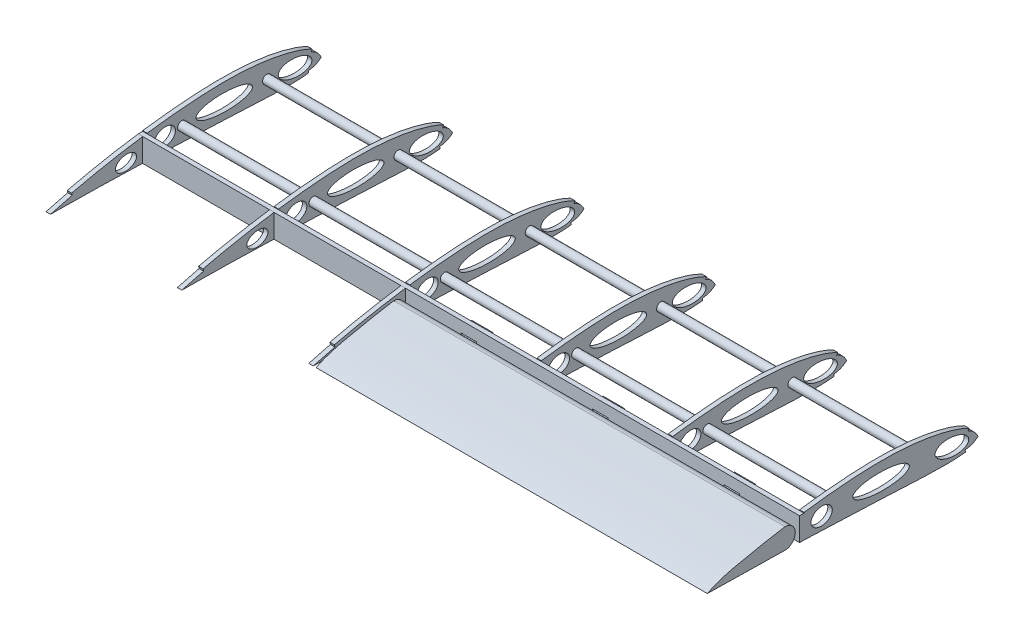
SolidWorks part; units mm, degrees
ref_plane "Front Plane" through (0, 0, 0) normal (0, 0, 1) x (1, 0, 0)
ref_plane "Top Plane" through (0, 0, 0) normal (0, 1, 0) x (1, 0, 0)
ref_plane "Right Plane" through (0, 0, 0) normal (1, 0, 0) x (0, 0, -1)
curve "Curve1"
  spline degree 3 poles (0, 0.2561, 197) (0, 1.149, 193.7201) (0, 2.9304, 187.176) (0, 6.1695, 174.0663) (0, 9.7483, 157.6722) (0, 13.2762, 137.9533) (0, 16.1679, 118.2496) (0, 18.2306, 98.5349) (0, 19.5171, 78.822) (0, 19.5301, 62.3654) (0, 18.621, 49.2257) (0, 17.4237, 39.3576) (0, 15.6579, 29.4682) (0, 13.5343, 21.2733) (0, 11.3895, 14.7062) (0, 9.3648, 9.7544) (0, 7.1751, 5.5294) (0, 4.5558, 1.862) (0, 0.3432, -1.3305) (0, -2.8786, 2.1154) (0, -4.1432, 5.6315) (0, -4.9968, 9.819) (0, -5.4308, 14.7645) (0, -5.7379, 21.3389) (0, -5.7149, 29.5521) (0, -5.4392, 39.4043) (0, -4.9143, 49.2495) (0, -4.3, 62.3829) (0, -3.5118, 78.7969) (0, -2.7716, 98.5006) (0, -1.9498, 118.198) (0, -1.2497, 137.8972) (0, -0.7348, 157.5981) (0, -0.4734, 174.0162) (0, -0.3012, 187.1497) (0, -0.2711, 193.7166) (0, -0.2561, 197) knots 0 0 0 0 0.025305 0.050488 0.10052 0.150191 0.199587 0.24874 0.297716 0.346601 0.371103 0.395726 0.42057 0.445825 0.458702 0.47192 0.485786 0.493461 0.506863 0.516148 0.522766 0.535269 0.547551 0.559786 0.584229 0.608681 0.633151 0.657622 0.706558 0.755482 0.804406 0.85332 0.902221 0.951113 0.975557 1 1 1 1
sketch "Sketch2" plane through (0, 0, 0) normal (1, 0, 0) x (0, 0, -1)
  line L0 (-197, 0.2561) -> (-197, -0.2561)
  line L1 (-197, 0) -> (0, 0) construction
  line L2 (-40, 17.4248) -> (-40, -5.373) construction
  line L3 (-100, 17.9747) -> (-100, -2.6983) construction
  line L4 (0, 0) -> (-40, 6.0259) construction
  line L5 (-40, 6.0259) -> (-100, 7.6382) construction
  line L6 (-100, 7.6382) -> (-197, 0) construction
  line L8 (-124.4398, 15.2116) -> (-124.4398, -1.7354)
  line L11 (-124.4398, 15.2116) -> (-127.6098, 15.2116)
  line L12 (-124.4398, 15.2116) -> (-124.4398, 8.8616)
  line L13 (-124.4398, 8.8616) -> (-127.6098, 8.8616)
  line L14 (-127.6098, 15.2116) -> (-127.6098, 8.8616)
  circle A0 centre (-100, 7.6382) radius 3
  circle A1 centre (-40, 6.0259) radius 3
  ellipse E0 centre (-70, 6.8321) end of major axis (-50.0072, 6.2948) minor radius 6.0022
  ellipse E1 centre (-20, 3.013) end of major axis (-31.8661, 4.8006) minor radius 6
  ellipse E2 centre (-111.963, 6.6962) end of major axis (-104.4861, 7.285) minor radius 6
  ellipse E3 centre (-139.3781, 4.5374) end of major axis (-131.9012, 5.1262) minor radius 5
  spline S0 degree 3 poles (-1051.5232, 1795.2139) (-419.8034, -115.8999) (-307.734, -26.8568) (-174.0663, 6.1695) (-157.6722, 9.7483) (-137.9533, 13.2762) (-118.2496, 16.1679) (-98.5349, 18.2306) (-78.822, 19.5171) (-62.3654, 19.5301) (-49.2257, 18.621) (-39.3576, 17.4237) (-29.4682, 15.6579) (-21.2733, 13.5343) (-14.7062, 11.3895) (-9.7544, 9.3648) (-5.5294, 7.1751) (-1.862, 4.5558) (1.3305, 0.3432) (-2.1154, -2.8786) (-5.6315, -4.1432) (-9.819, -4.9968) (-14.7645, -5.4308) (-21.3389, -5.7379) (-29.5521, -5.7149) (-39.4043, -5.4392) (-49.2495, -4.9143) (-62.3829, -4.3) (-78.7969, -3.5118) (-98.5006, -2.7716) (-118.198, -1.9498) (-137.8972, -1.2497) (-157.5981, -0.7348) (-174.0162, -0.4734) (-356.257, 1.9157) (-532.2805, -35.874) (-687.6692, 1915.6634) knots -0.924398 -0.924398 -0.924398 -0.924398 0.025305 0.050488 0.10052 0.150191 0.199587 0.24874 0.297716 0.346601 0.371103 0.395726 0.42057 0.445825 0.458702 0.47192 0.485786 0.493461 0.506863 0.516148 0.522766 0.535269 0.547551 0.559786 0.584229 0.608681 0.633151 0.657622 0.706558 0.755482 0.804406 0.85332 0.902221 0.951113 0.975557 2.258998 2.258998 2.258998 2.258998 only from (-197, 0.2561) to (-197, -0.2561) construction
  spline S1 degree 3 poles (-197, 0.2561) (-193.7201, 1.149) (-187.176, 2.9304) (-174.0663, 6.1695) (-157.6722, 9.7483) (-137.9533, 13.2762) (-118.2496, 16.1679) (-98.5349, 18.2306) (-78.822, 19.5171) (-62.3654, 19.5301) (-49.2257, 18.621) (-39.3576, 17.4237) (-29.4682, 15.6579) (-21.2733, 13.5343) (-14.7062, 11.3895) (-9.7544, 9.3648) (-5.5294, 7.1751) (-1.862, 4.5558) (1.3305, 0.3432) (-2.1154, -2.8786) (-5.6315, -4.1432) (-9.819, -4.9968) (-14.7645, -5.4308) (-21.3389, -5.7379) (-29.5521, -5.7149) (-39.4043, -5.4392) (-49.2495, -4.9143) (-62.3829, -4.3) (-78.7969, -3.5118) (-98.5006, -2.7716) (-118.198, -1.9498) (-137.8972, -1.2497) (-157.5981, -0.7348) (-174.0162, -0.4734) (-187.1497, -0.3012) (-193.7166, -0.2711) (-197, -0.2561) knots 0 0 0 0 0.025305 0.050488 0.10052 0.150191 0.199587 0.24874 0.297716 0.346601 0.371103 0.395726 0.42057 0.445825 0.458702 0.47192 0.485786 0.493461 0.506863 0.516148 0.522766 0.535269 0.547551 0.559786 0.584229 0.608681 0.633151 0.657622 0.706558 0.755482 0.804406 0.85332 0.902221 0.951113 0.975557 1 1 1 1
  point P36 (-98.5, 0)
  point P42 (-69.8388, 12.8321)
  point P43 (0, 0)
  point P45 (-69.8388, 19.4612)
  dimension "D3" = 6
  dimension "D4" = 6
  dimension "D12" = 5
  dimension "D13" = 3.17
  dimension "D17" = 15
  dimension "D1" = 40
  dimension "D2" = 60
  dimension "D5" = 40
  dimension "D6" = 12
  dimension "D7" = 12
  dimension "D8" = 15
  dimension "D9" = 12
  dimension "D10" = 24
  dimension "D11" = 12
  dimension "D15" = 20
  dimension "D16" = 10
  dimension "D14" = 6.35
extrude "Spars" add sketch "Sketch2" along normal blind 467 contours A1 | A0
extrude "Base Wing" add sketch "Sketch2<9>" along normal blind 3.175 contours A0 | E0 | A1 | E2 | E1 | S1 L0 | E3
sketch "Sketch2<9>" plane through (0, 0, 0) normal (1, 0, 0) x (0, 0, -1) same geometry as "Sketch2"
sketch "Sketch3" plane through (3.175, 0, 0) normal (1, 0, 0) x (0, 0, -1)
  line L0 (-197.1241, 0.224) -> (-177.7605, 5.2292)
  line L1 (-177.7605, 5.2292) -> (-197.1241, 0.224) construction
  line L2 (-177.7605, 5.2292) -> (-177.3632, 3.6922) construction
  line L3 (-197.1241, 0.224) -> (-196.7268, -1.313) construction
  line L4 (-177.3632, 3.6922) -> (-196.7268, -1.313) construction
  line L5 (0, 0) -> (-1.5698, 0.2365) construction
  line L6 (0, 0) -> (-40, 6.0259) construction
  line L7 (-7.8655, 8.3531) -> (-8.591, 6.9411)
  line L8 (-4.3591, 4.3441) -> (-3.3767, 5.5912) construction
  line L9 (-8.591, 6.9411) -> (-4.3591, 4.3441) construction
  line L10 (-4.3591, 4.3441) -> (-1.5698, 0.2365) construction
  line L11 (-5.3287, -3.9604) -> (-5.7651, -2.434) construction
  line L12 (-10.4332, -4.9861) -> (-10.6411, -3.4123)
  line L13 (-3.3767, 5.5912) -> (-2.3943, 6.8382)
  line L14 (-1.5698, 0.2365) -> (-5.7651, -2.434) construction
  line L15 (-10.6411, -3.4123) -> (-5.7651, -2.434) construction
  line L16 (0, 0) -> (1.5698, -0.2365)
  line L17 (-5.3287, -3.9604) -> (-4.8922, -5.4867)
  line L18 (-197.1241, 0.224) -> (-177.7605, 5.2292) construction
  line L23 (-197.1241, 0.224) -> (-197.5214, 1.761) construction
  line L24 (-177.7605, 5.2292) -> (-178.1578, 6.7662) construction
  line L25 (-197.5214, 1.761) -> (-178.1578, 6.7662) construction
  line L26 (-197.5214, 1.761) -> (-196.7268, -1.313)
  line L27 (-197.5214, 1.761) -> (-178.1578, 6.7662)
  line L28 (-196.7268, -1.313) -> (-177.3632, 3.6922)
  line L29 (-178.1578, 6.7662) -> (-177.3632, 3.6922)
  spline S0 degree 3 poles (-197, 0.2561) (-193.7201, 1.149) (-187.176, 2.9304) (-174.0663, 6.1695) (-157.6722, 9.7483) (-137.9533, 13.2762) (-118.2496, 16.1679) (-98.5349, 18.2306) (-78.822, 19.5171) (-62.3654, 19.5301) (-49.2257, 18.621) (-39.3576, 17.4237) (-29.4682, 15.6579) (-21.2733, 13.5343) (-14.7062, 11.3895) (-9.7544, 9.3648) (-5.5294, 7.1751) (-1.862, 4.5558) (1.3305, 0.3432) (-2.1154, -2.8786) (-5.6315, -4.1432) (-9.819, -4.9968) (-14.7645, -5.4308) (-21.3389, -5.7379) (-29.5521, -5.7149) (-39.4043, -5.4392) (-49.2495, -4.9143) (-62.3829, -4.3) (-78.7969, -3.5118) (-98.5006, -2.7716) (-118.198, -1.9498) (-137.8972, -1.2497) (-157.5981, -0.7348) (-174.0162, -0.4734) (-187.1497, -0.3012) (-193.7166, -0.2711) (-197, -0.2561) knots 0 0 0 0 0.025305 0.050488 0.10052 0.150191 0.199587 0.24874 0.297716 0.346601 0.371103 0.395726 0.42057 0.445825 0.458702 0.47192 0.485786 0.493461 0.506863 0.516148 0.522766 0.535269 0.547551 0.559786 0.584229 0.608681 0.633151 0.657622 0.706558 0.755482 0.804406 0.85332 0.902221 0.951113 0.975557 1 1 1 1 construction
  spline S1 degree 2 poles (-8.591, 6.9411) (-3.6378, 5.0995) (-1.5698, 0.2365) knots 0 0 0 1 1 1
  spline S2 degree 2 poles (-10.6411, -3.4123) (-5.4248, -3.2802) (-1.5698, 0.2365) knots 0 0 0 1 1 1
  spline S3 degree 3 poles (-7.8655, 8.3531) (-3.7436, 9.3316) (8.4481, -1.5787) (-6.8965, -7.2435) (-10.4332, -4.9861) knots 0 0 0 0 0.49814 1 1 1 1
  point P5 (-7.8655, 8.3531)
  point P25 (-10.4332, -4.9861)
  point P26 (-5.3287, -3.9604)
  point P27 (0, 0)
  dimension "D6" = 10
  dimension "D4" = 10
  dimension "D1" = 1.5875
  dimension "D2" = 20
  dimension "D3" = 1.5875
  dimension "D5" = 1.5875
pattern_linear "LPattern7" count 3 spacing 92.765 along (1, 0, 0) of "Base Wing"
extrude "Trailing Edge" cut sketch "Sketch3" against normal blind 3.175 contours L27 L29 L28 L26
extrude "Leading Edge" cut sketch "Sketch3<8>" against normal blind 3.175 contours S3 L12 S2 S1 L7
sketch "Sketch3<8>" plane through (3.175, 0, 0) normal (1, 0, 0) x (0, 0, -1) same geometry as "Sketch3"
pattern_linear "LPattern8" count 3 spacing 92.765 along (1, 0, 0) of "Trailing Edge", "Leading Edge"
extrude "Face" cut sketch "Sketch2<10>" along normal blind 3.175 contours L11 L14 L13 L12
sketch "Sketch2<10>" plane through (0, 0, 0) normal (1, 0, 0) x (0, 0, -1) same geometry as "Sketch2"
pattern_linear "LPattern9" count 3 spacing 92.765 along (1, 0, 0) of "Face"
ref_plane "SparPlane" through (0, 0, 127.6098) normal (0, 0, -1) x (-1, 0, 0)
sketch "Sketch12" plane through (0, 0, 127.6098) normal (0, 0, -1) x (-1, 0, 0)
  line L0 (0, 14.7629) -> (0, 8.8616)
  line L1 (0, 8.8616) -> (-3.175, 8.8616)
  line L2 (-3.175, 8.8616) -> (-3.175, -1.7384)
  line L3 (0, 14.7629) -> (-467, 14.7629)
  line L4 (-3.175, -1.7384) -> (-92.765, -1.7384)
  line L5 (-92.765, -1.7384) -> (-92.765, 8.8616)
  line L6 (-92.765, 8.8616) -> (-95.94, 8.8616)
  line L7 (-95.94, 8.8616) -> (-95.94, -1.7384)
  line L8 (-95.94, -1.7384) -> (-185.53, -1.7384)
  line L9 (-185.53, -1.7384) -> (-185.53, 8.8616)
  line L10 (-185.53, 8.8616) -> (-188.705, 8.8616)
  line L11 (-188.705, 8.8616) -> (-188.705, -1.7384)
  line L14 (-188.705, -1.7384) -> (-278.295, -1.7384)
  line L15 (-278.295, -1.7384) -> (-278.295, 8.8616)
  line L16 (-278.295, 8.8616) -> (-281.47, 8.8616)
  line L17 (-281.47, 8.8616) -> (-281.47, -1.7384)
  line L18 (-281.47, -1.7384) -> (-371.06, -1.7384)
  line L19 (-371.06, -1.7384) -> (-371.06, 8.8616)
  line L20 (-371.06, 8.8616) -> (-374.235, 8.8616)
  line L21 (-374.235, 8.8616) -> (-374.235, -1.7384)
  line L23 (-374.235, -1.7384) -> (-463.825, -1.7384)
  line L24 (-463.825, -1.7384) -> (-463.825, 8.8616)
  line L25 (-463.825, 8.8616) -> (-467, 8.8616)
  line L26 (-467, 8.8616) -> (-467, 14.7629)
  line L27 (-463.825, 14.7629) -> (-463.825, 8.8616) construction
  line L28 (-188.705, 14.7629) -> (-188.705, -1.7384) construction
  line L29 (-278.295, 14.7629) -> (-278.295, -1.7384) construction
  line L30 (-281.47, 14.7629) -> (-281.47, -1.7384) construction
  line L31 (-371.06, 14.7629) -> (-371.06, -1.7384) construction
  line L32 (-374.235, 14.7629) -> (-374.235, -1.7384) construction
  line L33 (-188.705, 6.5122) -> (-278.295, 6.5122)
  line L34 (-281.47, 6.5122) -> (-371.06, 6.5122)
  line L35 (-374.235, 6.5122) -> (-463.825, 6.5122)
  line L36 (-228, 6.0122) -> (-228, 7.0122)
  line L37 (-228, 6.0122) -> (-239, 6.0122)
  line L38 (-228, 7.0122) -> (-239, 7.0122)
  line L39 (-239, 6.0122) -> (-239, 7.0122)
  line L40 (-228, 6.0122) -> (-239, 7.0122) construction
  line L41 (-228, 7.0122) -> (-239, 6.0122) construction
  line L46 (-318.765, 4.0122) -> (-318.765, 9.0122)
  line L47 (-318.765, 9.0122) -> (-333.765, 9.0122)
  line L52 (-333.765, 4.0122) -> (-333.765, 9.0122)
  line L53 (-318.765, 4.0122) -> (-333.765, 4.0122)
  line L54 (-226, 4.0122) -> (-226, 9.0122)
  line L55 (-226, 9.0122) -> (-241, 9.0122)
  line L56 (-241, 4.0122) -> (-241, 9.0122)
  line L57 (-226, 4.0122) -> (-241, 4.0122)
  line L58 (-320.765, 6.0122) -> (-320.765, 7.0122)
  line L59 (-320.765, 6.0122) -> (-331.765, 6.0122)
  line L60 (-331.765, 6.0122) -> (-331.765, 7.0122)
  line L61 (-320.765, 7.0122) -> (-331.765, 7.0122)
  line L62 (-320.765, 6.0122) -> (-331.765, 7.0122) construction
  line L63 (-320.765, 7.0122) -> (-331.765, 6.0122) construction
  line L64 (-411.53, 4.0122) -> (-411.53, 9.0122)
  line L65 (-411.53, 9.0122) -> (-426.53, 9.0122)
  line L66 (-426.53, 4.0122) -> (-426.53, 9.0122)
  line L67 (-411.53, 4.0122) -> (-426.53, 4.0122)
  line L68 (-413.53, 6.0122) -> (-413.53, 7.0122)
  line L69 (-413.53, 6.0122) -> (-424.53, 6.0122)
  line L70 (-424.53, 6.0122) -> (-424.53, 7.0122)
  line L71 (-413.53, 7.0122) -> (-424.53, 7.0122)
  line L72 (-413.53, 6.0122) -> (-424.53, 7.0122) construction
  line L73 (-413.53, 7.0122) -> (-424.53, 6.0122) construction
  point P44 (-233.5, 6.5122)
  point P46 (-419.03, 6.5122)
  point P51 (-326.265, 6.5122)
  point P55 (-326.265, 6.5122)
  point P65 (-419.03, 6.5122)
  dimension "D1" = 467
  dimension "D2" = 10.6
  dimension "D3" = 92.765
  dimension "D4" = 11
  dimension "D5" = 1
  dimension "D6" = 2
  dimension "D7" = 3
extrude "Balsa Spar" add sketch "Sketch12" along normal blind 3.175 contours L3 L26 L25 L24 L23 L21 L20 L19 L18 L17 L16 L15 L14 L11 L10 L9 L8 L7 L6 L5 L4 L2 L1 L0
ref_plane "Secondary Plane" through (278.295, 0, 0) normal (1, 0, 0) x (0, 0, -1)
sketch "Sketch13" plane through (278.295, 0, 0) normal (1, 0, 0) x (0, 0, -1)
  line L0 (-127.6098, 8.8616) -> (-124.4398, 8.8616)
  line L1 (-127.6098, 8.8616) -> (-127.6098, -1.7384)
  line L2 (-127.6098, -1.7384) -> (-124.4348, -1.7356)
  line L3 (-124.4398, 8.8616) -> (-124.4398, 14.7629)
  line L4 (-124.4398, 15.2116) -> (-124.4398, 14.7629)
  line L6 (-124.4398, 14.7629) -> (-124.4348, 14.7629)
  line L7 (-124.4348, 14.7629) -> (-124.4348, -1.7356)
  line L11 (-124.4398, 14.7629) -> (-124.4348, 14.7629)
  line L15 (-124.4398, 14.7629) -> (-124.4398, 8.8616)
  line L16 (-124.4398, 15.2116) -> (-124.4398, 14.7629)
  line L17 (-124.4398, 15.2116) -> (-124.4398, 14.7629)
  line L20 (-10.4332, -4.9861) -> (-10.6411, -3.4123)
  line L21 (-10.4332, -4.9861) -> (-10.6411, -3.4123)
  line L22 (-8.591, 6.9411) -> (-7.8655, 8.3531)
  line L23 (-8.591, 6.9411) -> (-7.8655, 8.3531)
  circle A0 centre (-40, 6.0259) radius 3 construction
  circle A1 centre (-40, 6.0259) radius 3
  circle A2 centre (-100, 7.6382) radius 3 construction
  circle A3 centre (-100, 7.6382) radius 3
  ellipse E0 centre (-111.963, 6.6962) end of major axis (-104.4861, 7.285) minor radius 6 construction
  ellipse E1 centre (-70, 6.8321) end of major axis (-50.0072, 6.2948) minor radius 6.0022 construction
  ellipse E2 centre (-20, 3.013) end of major axis (-8.1339, 1.2254) minor radius 6 construction
  ellipse E3 centre (-111.963, 6.6962) end of major axis (-104.4861, 7.285) minor radius 6
  ellipse E4 centre (-70, 6.8321) end of major axis (-50.0072, 6.2948) minor radius 6.0022
  ellipse E5 centre (-20, 3.013) end of major axis (-8.1339, 1.2254) minor radius 6
  parabola Q2 (-10.6411, -3.4123) -> (-1.5698, 0.2365) focus (-8.21, 3.6444) apex (-5.7651, -2.434)
  parabola Q3 (-10.6411, -3.4123) -> (-1.5698, 0.2365) focus (-8.21, 3.6444) apex (-5.7651, -2.434)
  parabola Q4 (-1.5698, 0.2365) -> (-8.591, 6.9411) focus (-8.2542, 0.2651) apex (-4.3591, 4.3441)
  parabola Q5 (-1.5698, 0.2365) -> (-8.591, 6.9411) focus (-8.2542, 0.2651) apex (-4.3591, 4.3441)
  spline S2 degree 3 poles (-1367.7155, -2590.3642) (-923.6568, -46.7157) (-512.7824, 14.5145) (-98.5006, -2.7716) (-78.7969, -3.5118) (-62.3829, -4.3) (-49.2495, -4.9143) (-39.4043, -5.4392) (-29.5521, -5.7149) (-21.3389, -5.7379) (43.0686, -2.729) (98.3082, 46.1829) (278.6729, 2978.1004) knots -2.436694 -2.436694 -2.436694 -2.436694 0.552208 0.601132 0.650055 0.698992 0.723462 0.747933 0.772385 0.796827 0.809062 1.252024 1.252024 1.252024 1.252024 only from (-124.4348, -1.7356) to (-10.4332, -4.9861)
  spline S3 degree 3 poles (-2916.9485, -710.3536) (73.3325, -105.9441) (37.3308, -9.8882) (-14.7062, 11.3895) (-21.2733, 13.5343) (-29.4682, 15.6579) (-39.3576, 17.4237) (-49.2257, 18.621) (-62.3654, 19.5301) (-78.822, 19.5171) (-98.5349, 18.2306) (-428.5049, -16.293) (-710.2974, -378.6878) (-1008.0238, 2779.7932) knots -0.204448 -0.204448 -0.204448 -0.204448 0.1894 0.202617 0.215494 0.240749 0.265593 0.290217 0.314719 0.363604 0.412579 0.461733 2.832769 2.832769 2.832769 2.832769 only from (-7.8655, 8.3531) to (-124.4398, 15.2116)
  spline S4 degree 3 poles (-124.4348, -1.7356) (-122.3565, -1.8115) (-113.7109, -2.137) (-98.5006, -2.7716) (-78.7969, -3.5118) (-62.3829, -4.3) (-49.2495, -4.9143) (-39.4043, -5.4392) (-29.5521, -5.7149) (-21.3389, -5.7379) (-14.96, -5.4399) (-11.8784, -5.177) (-10.4332, -4.9861) knots 0.536725 0.536725 0.536725 0.536725 0.552208 0.601132 0.650055 0.698992 0.723462 0.747933 0.772385 0.796827 0.809062 0.819888 0.819888 0.819888 0.819888
  spline S5 degree 3 poles (-7.8655, 8.3531) (-8.5192, 8.689) (-10.7997, 9.7922) (-14.7062, 11.3895) (-21.2733, 13.5343) (-29.4682, 15.6579) (-39.3576, 17.4237) (-49.2257, 18.621) (-62.3654, 19.5301) (-78.822, 19.5171) (-98.5349, 18.2306) (-113.7356, 16.6402) (-122.3616, 15.4993) (-124.4398, 15.2116) knots 0.183969 0.183969 0.183969 0.183969 0.1894 0.202617 0.215494 0.240749 0.265593 0.290217 0.314719 0.363604 0.412579 0.461733 0.477351 0.477351 0.477351 0.477351
  dimension "D1" = 0
extrude "Secondary Base Wing" add sketch "Sketch13" along normal blind 3.175 contours L3 L0 L1 L2 S4 L21 Q3 Q5 L23 S5 L17 | E4 | E3 | E5 | A1 | A3
pattern_linear "LPattern11" count 3 spacing 92.765 along (1, 0, 0) of "Secondary Base Wing"
ref_plane "Insert Plane" through (0, 0, 124.4348) normal (0, 0, -1) x (-1, 0, 0)
sketch "Sketch15" plane through (0, 0, 124.4348) normal (0, 0, -1) x (-1, 0, 0)
  line L0 (-413.53, 6.0122) -> (-413.53, 7.0122) construction
  line L1 (-413.53, 6.0122) -> (-424.53, 6.0122) construction
  line L2 (-424.53, 6.0122) -> (-424.53, 7.0122) construction
  line L3 (-413.53, 7.0122) -> (-424.53, 7.0122) construction
  line L4 (-426.53, 4.0122) -> (-426.53, 9.0122) construction
  line L5 (-411.53, 4.0122) -> (-426.53, 4.0122) construction
  line L6 (-411.53, 4.0122) -> (-411.53, 9.0122) construction
  line L7 (-411.53, 9.0122) -> (-426.53, 9.0122) construction
  line L8 (-228, 6.0122) -> (-228, 7.0122) construction
  line L9 (-228, 6.0122) -> (-239, 6.0122) construction
  line L10 (-239, 6.0122) -> (-239, 7.0122) construction
  line L11 (-228, 7.0122) -> (-239, 7.0122) construction
  line L12 (-241, 4.0122) -> (-241, 9.0122) construction
  line L13 (-226, 4.0122) -> (-241, 4.0122) construction
  line L14 (-226, 4.0122) -> (-226, 9.0122) construction
  line L15 (-226, 9.0122) -> (-241, 9.0122) construction
  line L16 (-318.765, 4.0122) -> (-318.765, 9.0122) construction
  line L17 (-318.765, 4.0122) -> (-333.765, 4.0122) construction
  line L18 (-333.765, 4.0122) -> (-333.765, 9.0122) construction
  line L19 (-318.765, 9.0122) -> (-333.765, 9.0122) construction
  line L20 (-331.765, 6.0122) -> (-331.765, 7.0122) construction
  line L21 (-320.765, 6.0122) -> (-331.765, 6.0122) construction
  line L22 (-320.765, 7.0122) -> (-331.765, 7.0122) construction
  line L23 (-320.765, 6.0122) -> (-320.765, 7.0122) construction
  line L24 (-413.53, 6.0122) -> (-413.53, 7.0122)
  line L25 (-413.53, 6.0122) -> (-424.53, 6.0122)
  line L26 (-424.53, 6.0122) -> (-424.53, 7.0122)
  line L27 (-413.53, 7.0122) -> (-424.53, 7.0122)
  line L28 (-426.53, 4.0122) -> (-426.53, 9.0122)
  line L29 (-411.53, 4.0122) -> (-426.53, 4.0122)
  line L30 (-411.53, 4.0122) -> (-411.53, 9.0122)
  line L31 (-411.53, 9.0122) -> (-426.53, 9.0122)
  line L32 (-228, 6.0122) -> (-228, 7.0122)
  line L33 (-228, 6.0122) -> (-239, 6.0122)
  line L34 (-239, 6.0122) -> (-239, 7.0122)
  line L35 (-228, 7.0122) -> (-239, 7.0122)
  line L36 (-241, 4.0122) -> (-241, 9.0122)
  line L37 (-226, 4.0122) -> (-241, 4.0122)
  line L38 (-226, 4.0122) -> (-226, 9.0122)
  line L39 (-226, 9.0122) -> (-241, 9.0122)
  line L40 (-318.765, 4.0122) -> (-318.765, 9.0122)
  line L41 (-318.765, 4.0122) -> (-333.765, 4.0122)
  line L42 (-333.765, 4.0122) -> (-333.765, 9.0122)
  line L43 (-318.765, 9.0122) -> (-333.765, 9.0122)
  line L44 (-331.765, 6.0122) -> (-331.765, 7.0122)
  line L45 (-320.765, 6.0122) -> (-331.765, 6.0122)
  line L46 (-320.765, 7.0122) -> (-331.765, 7.0122)
  line L47 (-320.765, 6.0122) -> (-320.765, 7.0122)
extrude "Inserts" add sketch "Sketch15" along normal blind 3.175
pattern_linear "LPattern12" count 2 spacing 3.175 along (0, 0, -1) of "Inserts"
ref_plane "Aileron Plane" through (190.705, 0, 0) normal (1, 0, 0) x (0, 0, -1)
sketch "Sketch17" plane through (190.705, 0, 0) normal (1, 0, 0) x (0, 0, -1)
  line L0 (-137.845, -1.2822) -> (-137.845, 13.1882) construction
  line L1 (-137.845, 5.953) -> (-192.7184, -0.2769) construction
  line L2 (-165.2817, 2.8381) -> (-165.8594, 7.9262) construction
  line L3 (-127.6098, -1.6216) -> (-127.6098, 14.7629)
  line L4 (-177.7605, 5.2292) -> (-177.3632, 3.6922)
  line L5 (-177.3632, 3.6922) -> (-192.7184, -0.2769)
  line L6 (-127.6098, -1.6216) -> (-127.6098, 14.7629)
  line L7 (-177.7605, 5.2292) -> (-177.3632, 3.6922)
  line L8 (-177.3632, 3.6922) -> (-192.7184, -0.2769)
  line L9 (-165.2817, 2.8381) -> (-137.845, 5.953) construction
  line L10 (-165.2817, 2.8381) -> (-137.845, 5.953) construction
  line L11 (-137.845, 5.953) -> (-151.5634, 4.3956) construction
  line L12 (-151.5634, 4.3956) -> (-152.2748, 10.6623) construction
  line L13 (-192.7184, -0.2769) -> (-137.845, -1.2822)
  arc A0 (-137.845, 13.1882) -> (-137.845, -1.2822) centre (-137.845, 5.953) cw
  spline S0 degree 1 poles (-137.845, 13.1882) (-152.2748, 10.6623) knots 0 0 1 1
  spline S1 degree 3 poles (-137.845, 13.1882) (-147.2462, 11.7369) (-165.7323, 8) (-184.2505, 4.0667) (-192.7184, -0.2769) knots 0 0 0 0 0.503218 1 1 1 1
  spline S2 degree 3 poles (-755.0077, 2911.5208) (-583.0658, -47.6094) (-381.5956, 2.2478) (-174.0162, -0.4734) (-157.5981, -0.7348) (284.8785, -12.2997) (716.4734, -159.5093) (1182.3538, 2510.7435) knots -0.630495 -0.630495 -0.630495 -0.630495 0.84159 0.866034 0.914926 0.963827 4.161051 4.161051 4.161051 4.161051 only from (-192.7184, -0.2769) to (-127.6098, -1.6216)
  spline S3 degree 3 poles (793.2444, -2775.7791) (428.7441, -71.8713) (123.9697, 60.136) (-157.6722, 9.7483) (-388.6317, -40.6699) (-579.8547, -228.2766) (82.11, -2940.561) knots -1.9547 -1.9547 -1.9547 -1.9547 0.075147 0.124817 0.17485 1.834535 1.834535 1.834535 1.834535 only from (-127.6098, 14.7629) to (-177.7605, 5.2292)
  spline S4 degree 3 poles (-192.7184, -0.2769) (-190.8622, -0.2868) (-185.7226, -0.3199) (-174.0162, -0.4734) (-157.5981, -0.7348) (-141.035, -1.1677) (-131.0396, -1.5005) (-127.6098, -1.6216) knots 0.827772 0.827772 0.827772 0.827772 0.84159 0.866034 0.914926 0.963827 0.989375 0.989375 0.989375 0.989375
  spline S5 degree 3 poles (-127.6098, 14.7629) (-131.0445, 14.2663) (-141.0695, 12.7187) (-157.6722, 9.7483) (-170.9147, 6.8575) (-177.607, 5.2657) (-177.7605, 5.2292) knots 0.049313 0.049313 0.049313 0.049313 0.075147 0.124817 0.17485 0.176024 0.176024 0.176024 0.176024
  point P8 (-130.6098, 5.953)
  dimension "D2" = 3
  dimension "D1" = 0
extrude "Aileron" add sketch "Sketch17" along normal up to surface (276.295 mm away) separate body contours S1 A0 L13 up to face at (467, 4.1415, 66.7373)
extrude "Holes" cut sketch "Sketch15<3>" along normal blind 3.175 and the other way blind 16 contours L35 L34 L33 L32 | L27 L26 L25 L24 | L46 L44 L45 L47
sketch "Sketch15<3>" plane through (0, 0, 124.4348) normal (0, 0, -1) x (-1, 0, 0) same geometry as "Sketch15"
